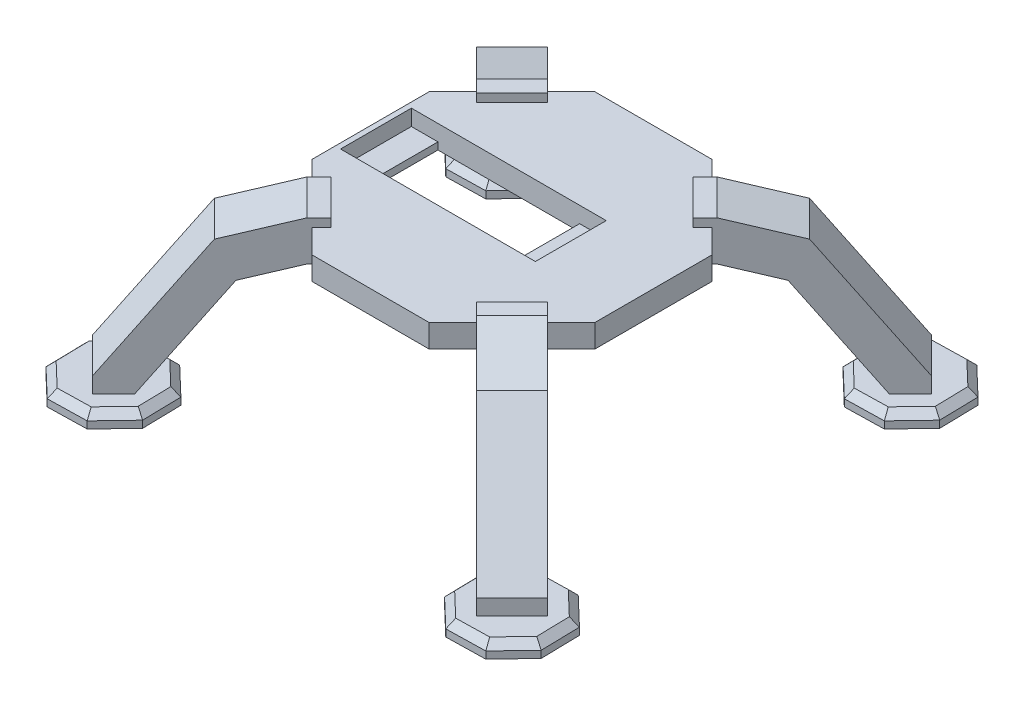
SolidWorks part; units mm, degrees
ref_plane "Front Plane" through (0, 0, 0) normal (0, 0, 1) x (1, 0, 0)
ref_plane "Top Plane" through (0, 0, 0) normal (0, 1, 0) x (1, 0, 0)
ref_plane "Right Plane" through (0, 0, 0) normal (1, 0, 0) x (0, 0, -1)
sketch "Sketch1" plane through (0, 0, 0) normal (0, 1, 0) x (1, 0, 0)
  line L6 (39.9, -16.5271) -> (39.9, 16.5271)
  line L10 (16.6, 10) -> (16.6, -10)
  line L15 (16.6, -10) -> (-38.4, -10)
  line L16 (-38.4, -10) -> (-38.4, 10)
  line L17 (-38.4, 10) -> (16.6, 10)
  line L18 (-30.9, 10) -> (-30.9, -10)
  line L19 (-30.9, -10) -> (9.1, -10)
  line L20 (9.1, -10) -> (9.1, 10)
  line L21 (39.9, 16.5271) -> (16.5271, 39.9)
  line L22 (16.5271, 39.9) -> (-16.5271, 39.9)
  line L23 (-16.5271, 39.9) -> (-39.9, 16.5271)
  line L24 (-39.9, 16.5271) -> (-39.9, -16.5271)
  line L25 (-39.9, -16.5271) -> (-16.5271, -39.9)
  line L26 (-16.5271, -39.9) -> (16.5271, -39.9)
  line L27 (16.5271, -39.9) -> (39.9, -16.5271)
  circle A0 centre (0, 0) radius 4.5647
  circle A1 centre (0, 0) radius 39.9 construction
  point P0 (0, 0)
  point P21 (16.6, 0)
  point P27 (-10.9, -10)
  point P28 (-10.9, -10)
  dimension "D2" = 1.5
  dimension "D7" = 20
  dimension "D8" = 55
  dimension "D9" = 16.6
  dimension "D10" = 40
extrude "Boss-Extrude1" add sketch "Sketch1" along normal blind 6.5 contours L26 L24 L16 L17 L10 L15 | L18 L17 L16 L15 | L20 L15 L10 L17 region at (27.4156, 0, 27.4156) region at (12.85, 0, 0) region at (-34.65, 0, 0)
extrude "Cut-Extrude1" cut sketch "Sketch1<3>" along normal up to next from offset 2 contours L20 L15 L10 L17 | L18 L17 L16 L15 region at (12.85, 0, 0) region at (-34.65, 0, 0)
sketch "Sketch1<3>" plane through (0, 0, 0) normal (0, 1, 0) x (1, 0, 0) same geometry as "Sketch1"
ref_plane "Plane1" through (0, 0, 0) normal (0.7071, 0, 0.7071) x (0.7071, 0, -0.7071)
sketch "Sketch2" plane through (0, 0, 0) normal (0.7071, 0, 0.7071) x (0.7071, 0, -0.7071)
  line L32 (-39.9, 6.5) -> (-39.9, 0)
  line L38 (-39.9, 0) -> (-36.1401, 0)
  line L39 (-39.9, 0) -> (-16.5271, 0) construction
  line L40 (-36.1401, 0) -> (-36.1401, -2.3919)
  line L42 (-55.1022, -6.3996) -> (-75.3523, -34.234)
  line L43 (-75.3523, -34.234) -> (-83.7438, -34.234)
  line L44 (-83.7438, -34.234) -> (-83.7438, -29.7803)
  line L45 (-83.7438, -29.7803) -> (-59.4073, 3.671)
  line L46 (-59.4073, 3.671) -> (-40.8809, 8.8919)
  line L47 (-40.8809, 8.8919) -> (-36.1401, 8.8919)
  line L48 (-36.1401, 8.8919) -> (-36.1401, 6.5)
  line L49 (-39.9, 6.5) -> (-16.5271, 6.5) construction
  line L50 (-36.1401, 6.5) -> (-39.9, 6.5)
  line L51 (-36.1401, -2.3919) -> (-40.8809, -2.3919)
  line L52 (-55.1022, -6.3996) -> (-40.8809, -2.3919)
  point P7 (-40.8809, -2.3919)
  point P17 (0, 0)
  point P19 (-82.9168, -33.2083)
  point P20 (-92.6677, -26.8864)
  point P21 (0, 0)
  point P22 (-58.3627, 8.8919)
  point P23 (-66.8787, -34.9511)
  point P24 (-83.7438, -29.9417)
  point P25 (-75.3523, -34.234)
  point P26 (-59.4073, 3.671)
  point P27 (0, 0)
extrude "Boss-Extrude2" add sketch "Sketch2" along normal mid plane 14.14 separate body
ref_plane "Plane2" through (0, 0, 0) normal (-1, 0, 0) x (0, 0, 1)
ref_plane "Plane3" through (0, 0, 0) normal (0, 0, 1) x (1, 0, 0)
sketch "Sketch5" plane through (-4.9992, 0, -4.9992) normal (-0.7071, 0, -0.7071) x (-0.7071, 0, 0.7071)
  line L59 (44.6921, -1.1708) -> (55.5422, 1.7365)
  line L92 (71.4, -30) -> (43.4, -2) construction
  line L131 (55.5422, 1.7365) -> (52.6349, -9.1136)
  line L132 (52.6349, -9.1136) -> (44.6921, -1.1708)
  line L133 (41.4, 7) -> (41.4, -0.5)
  line L136 (41.4, -0.5) -> (55.1018, 3.1714)
  line L143 (55.1018, 3.1714) -> (53.8841, 7)
  line L144 (56.7669, 0.5117) -> (64.7098, -7.4311)
  line L145 (64.7098, -7.4311) -> (53.8597, -10.3384)
  line L146 (53.8597, -10.3384) -> (56.7669, 0.5117)
  line L147 (54.1859, 8.5) -> (68.4636, -28.3302) construction
  line L149 (52.2947, 8.5) -> (65.9161, -34.3302) construction
  line L150 (35.9, 8.5) -> (54.1859, 8.5) construction
  line L151 (68.4636, -34.3302) -> (56.4636, -34.3302) construction
  line L152 (57.4, -16) -> (60.8377, -9.9151) construction
  line L185 (53.8841, 7) -> (41.4, 7)
  line L186 (39.9, 6.5) -> (39.9, 0) construction
  line L187 (45.043, -2) -> (35.9, -2) construction
  line L188 (55.0844, -11.5631) -> (65.9345, -8.6558)
  line L192 (65.9345, -8.6558) -> (63.0272, -19.5059)
  line L193 (63.0272, -19.5059) -> (55.0844, -11.5631)
  line L196 (75.1021, -17.8234) -> (64.252, -20.7307)
  line L197 (64.252, -20.7307) -> (67.1593, -9.8806)
  line L198 (67.1593, -9.8806) -> (75.1021, -17.8234)
  line L199 (65.4767, -21.9554) -> (76.3268, -19.0481)
  line L200 (76.3268, -19.0481) -> (73.4195, -29.8982)
  line L201 (73.4195, -29.8982) -> (65.4767, -21.9554)
  line L202 (85.4944, -28.2157) -> (74.6443, -31.123)
  line L203 (74.6443, -31.123) -> (77.5516, -20.2729)
  line L204 (77.5516, -20.2729) -> (85.4944, -28.2157)
  line L205 (75.869, -32.3477) -> (86.7191, -29.4404)
  line L206 (86.7191, -29.4404) -> (83.8118, -40.2905)
  line L207 (83.8118, -40.2905) -> (75.869, -32.3477)
  line L211 (85.0366, -41.5153) -> (87.9439, -30.6652)
  line L212 (95.8867, -38.608) -> (85.0366, -41.5153)
  line L213 (87.9439, -30.6652) -> (95.8867, -38.608)
  line L214 (87.5619, -32.0905) -> (85.0366, -41.5153)
  line L215 (85.0366, -41.5153) -> (76.3515, -32.8302)
  line L216 (76.3515, -32.8302) -> (65.1943, -32.8302)
  line L217 (65.1943, -32.8302) -> (65.1943, 38.2405)
  line L218 (65.1943, 38.2405) -> (87.5619, -32.0905)
  line L219 (68.4636, -28.3302) -> (68.4636, -34.3302) construction
  point P18 (59.1189, -12.9575)
  point P47 (41.4, -0.5174)
  point P48 (51.4262, 2.7117)
  dimension "D1" = 1.5
  dimension "D2" = 1.5
  dimension "D3" = 1.5
  dimension "D8" = 1.5
  dimension "D9" = 1.5
  dimension "D10" = 3.2692
  dimension "D11" = 1.5
  dimension "D4" = 1.5
  dimension "D5" = 1.5
  dimension "D6" = 1.5
  dimension "D12" = 1.5
  dimension "D13" = 1.5
  dimension "D7" = 4
extrude "Cut-Extrude2" [suppressed] cut sketch "Sketch5" against normal up to next
sketch "Sketch8" plane through (-16.214, -34.234, -16.214) normal (0, 1, 0) x (0.7071, 0, -0.7071)
  line L10 (-75.3523, -30) -> (-75.3523, -15.86) construction
  line L11 (-74.3165, -9.4685) -> (-85.3675, -9.712)
  line L12 (-85.3675, -9.712) -> (-93.0095, -17.6984)
  line L13 (-93.0095, -17.6984) -> (-92.7661, -28.7494)
  line L14 (-92.7661, -28.7494) -> (-84.7797, -36.3915)
  line L15 (-84.7797, -36.3915) -> (-73.7287, -36.148)
  line L16 (-73.7287, -36.148) -> (-66.0866, -28.1616)
  line L17 (-66.0866, -28.1616) -> (-66.3301, -17.1106)
  line L18 (-66.3301, -17.1106) -> (-74.3165, -9.4685)
  line L21 (-83.7438, -15.86) -> (-75.3523, -15.86) construction
  circle A0 centre (-79.5481, -22.93) radius 13.343 construction
  point P1 (-82.8854, -24.2131)
  point P3 (-88.3493, -22.93)
  point P5 (-88.2126, -22.93)
  point P17 (-75.3523, -22.93)
  point P20 (-79.5481, -15.86)
  point P24 (-67.6218, -22.93)
extrude "Boss-Extrude4" add sketch "Sketch8" against normal blind 4
chamfer "Chamfer3" distance 2 angle 45 8 edges at (-47.0242, -34.234, 46.6086) (-42.9092, -34.234, 55.9551) (-46.6086, -34.234, 65.4738) (-55.9551, -34.234, 69.5887) (-65.4738, -34.234, 65.8894) (-69.5887, -34.234, 56.5429) (-65.8894, -34.234, 47.0242) (-56.5429, -34.234, 42.9092)
ref_axis "Axis1" through (0, 0, 0) along (0, 1, 0)
pattern_circular "CirPattern7" count 4 every 90 about axis through (0, 0, 0) along (0, 1, 0) of bodies 103 117 113
equation "\"D2@Sketch5\"=\"D1@Sketch5\""
equation "\"D3@Sketch5\"=\"D2@Sketch5\""
equation "\"D8@Sketch5\"=\"D1@Sketch5\""
equation "\"D9@Sketch5\"=\"D1@Sketch5\""
equation "\"D10@Sketch5\"=\"D9@Sketch5\""
equation "\"D11@Sketch5\"=\"D9@Sketch5\""
equation "\"D4@Sketch5\"=\"D3@Sketch5\""
equation "\"D5@Sketch5\"=\"D4@Sketch5\""
equation "\"D6@Sketch5\"=\"D4@Sketch5\""
equation "\"D12@Sketch5\"=\"D4@Sketch5\""
equation "\"D13@Sketch5\"=\"D5@Sketch5\""
